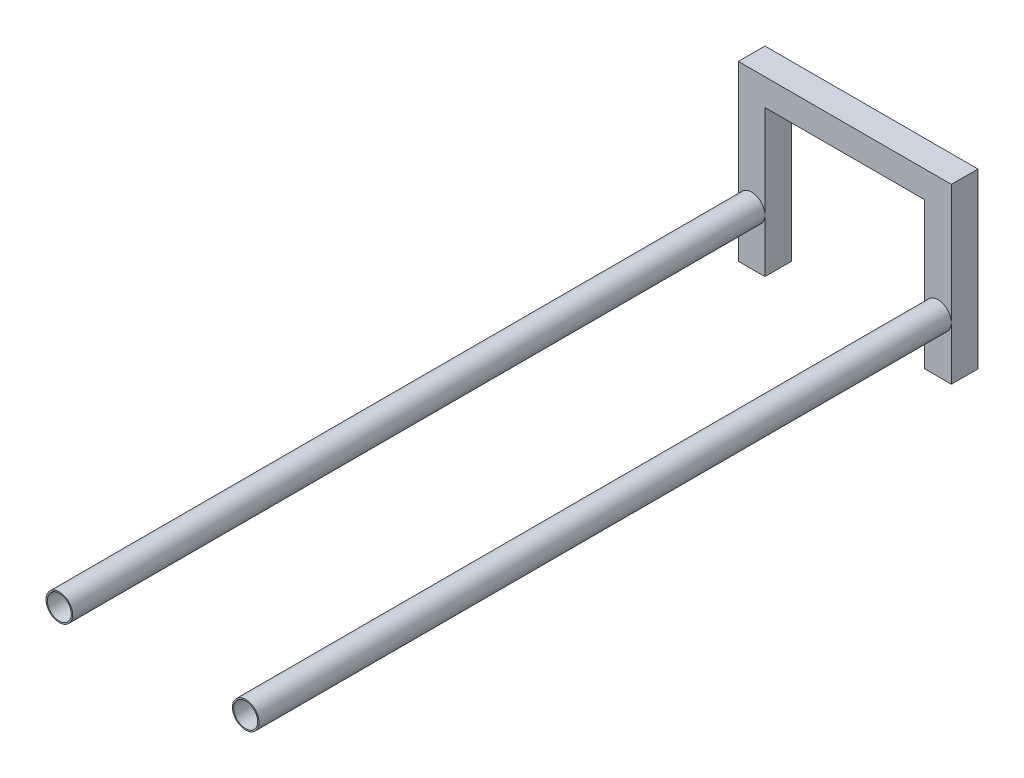
SolidWorks part; units mm, degrees
ref_plane "Front Plane" through (0, 0, 0) normal (0, 0, 1) x (1, 0, 0)
ref_plane "Top Plane" through (0, 0, 0) normal (0, 1, 0) x (1, 0, 0)
ref_plane "Right Plane" through (0, 0, 0) normal (1, 0, 0) x (0, 0, -1)
sketch "Sketch1" plane through (0, 0, 0) normal (0, 0, 1) x (1, 0, 0)
  line L0 (-88.9, 0) -> (0, 0) construction
  line L1 (0, 0) -> (0, 37.2678) construction
  circle A0 centre (-88.9, 0) radius 12.7
  circle A1 centre (-88.9, 0) radius 11.4554
  circle A2 centre (88.9, 0) radius 12.7
  circle A3 centre (88.9, 0) radius 11.4554
  dimension "D2" = 25.4
  dimension "D1" = 88.9
  dimension "D3" = 1.2446
extrude "Boss-Extrude1" add sketch "Sketch1" along normal blind 660.4
sketch "Sketch2" plane through (0, 0, 0) normal (0, 0, -1) x (-1, 0, 0)
  line L0 (88.9, 0) -> (88.9, 101.6) construction
  line L1 (88.9, 101.6) -> (-88.9, 101.6) construction
  line L2 (-88.9, 101.6) -> (-88.9, 0) construction
  line L3 (101.6, 0) -> (101.6, 114.3)
  line L4 (101.6, 114.3) -> (-101.6, 114.3)
  line L5 (-101.6, 114.3) -> (-101.6, 0)
  line L6 (76.2, 0) -> (76.2, 88.9)
  line L7 (76.2, 88.9) -> (-76.2, 88.9)
  line L8 (-76.2, 88.9) -> (-76.2, 0)
  line L9 (101.6, 0) -> (101.6, -50.8)
  line L10 (101.6, -50.8) -> (76.2, -50.8)
  line L11 (76.2, -50.8) -> (76.2, 0)
  line L12 (0, 0) -> (0, 101.6) construction
  line L13 (-101.6, -50.8) -> (-76.2, -50.8)
  line L14 (-101.6, 0) -> (-101.6, -50.8)
  line L15 (-76.2, -50.8) -> (-76.2, 0)
  point P6 (0, 101.6)
  dimension "D1" = 101.6
  dimension "D4" = 50.8
  dimension "D2" = 12.7
  dimension "D3" = 12.7
extrude "Boss-Extrude2" add sketch "Sketch2" along normal blind 25.4
shell "Shell1" thickness 1.2446 removed face at (88.9, -50.8, -12.7) removed face at (-88.9, -50.8, -12.7)
